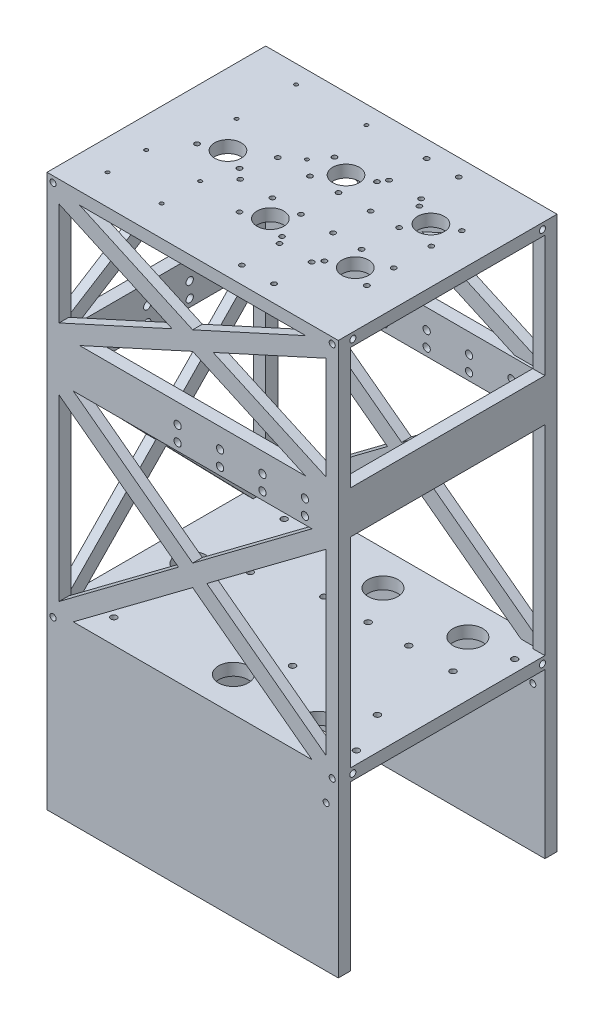
SolidWorks part; units mm, degrees
ref_plane "Front Plane" through (0, 0, 0) normal (0, 0, 1) x (1, 0, 0)
ref_plane "Top Plane" through (0, 0, 0) normal (0, 1, 0) x (1, 0, 0)
ref_plane "Right Plane" through (0, 0, 0) normal (1, 0, 0) x (0, 0, -1)
sketch "Sketch1" plane through (0, 0, 0) normal (0, 1, 0) x (1, 0, 0)
  line L0 (0, 90.15) -> (0, -90.15) construction
  line L1 (-120.075, 0) -> (120.075, 0) construction
  line L2 (-120.075, 90.15) -> (120.075, 90.15)
  line L3 (120.075, 90.15) -> (120.075, -90.15)
  line L4 (120.075, -90.15) -> (-120.075, -90.15)
  line L5 (-120.075, -90.15) -> (-120.075, 90.15)
  dimension "D1" = 240.15
  dimension "D2" = 180.3
extrude "Boss-Extrude1" add sketch "Sketch1" along normal blind 145
sketch "Sketch2" plane through (0, 145, 0) normal (0, 1, 0) x (1, 0, 0)
  line L0 (0, 90.15) -> (0, -90.15) construction
  line L1 (120.075, 90.15) -> (-120.075, 90.15) construction
  line L2 (-120.075, -90.15) -> (120.075, -90.15) construction
  line L3 (-120.075, 0) -> (120.075, 0) construction
  line L4 (-120.075, 90.15) -> (-120.075, -90.15) construction
  line L5 (120.075, -90.15) -> (120.075, 90.15) construction
  line L6 (75.105, -61.65) -> (75.105, -90.15) construction
  line L7 (75.105, -61.65) -> (120.075, -61.65) construction
  line L8 (75.105, -61.65) -> (5.105, -61.65) construction
  circle A0 centre (75.105, -61.65) radius 12.25
  circle A1 centre (5.105, -61.65) radius 12.25
  circle A2 centre (75.105, 61.65) radius 12.25
  circle A3 centre (5.105, 61.65) radius 12.25
  circle A4 centre (-91.515, 0) radius 12.25
  dimension "D3" = 24.5
  dimension "24.5" = 24.5
  dimension "D6" = 24.5
  dimension "D7" = 28.56
  dimension "D1" = 44.97
  dimension "D2" = 28.5
  dimension "D4" = 70
extrude "Cut-Extrude1" cut sketch "Sketch2" against normal blind 120
sketch "Sketch3" plane through (120.075, 0, 0) normal (1, 0, 0) x (0, 0, -1)
  line L0 (0, 145) -> (0, 0) construction
  line L1 (-90.15, 145) -> (90.15, 145) construction
  line L2 (-90.15, 72.5) -> (90.15, 72.5) construction
  line L3 (-90.15, 145) -> (-90.15, 0) construction
  line L4 (90.15, 145) -> (90.15, 0) construction
  line L5 (-80.21, 135.06) -> (80.21, 135.06)
  line L6 (80.21, 135.06) -> (80.21, 0)
  line L7 (-90.15, 0) -> (90.15, 0) construction
  line L8 (80.21, 0) -> (-80.21, 0)
  line L9 (-80.21, 0) -> (-80.21, 135.06)
  dimension "D1" = 9.94
  dimension "D2" = 9.94
  dimension "D3" = 9.94
extrude "Cut-Extrude3" cut sketch "Sketch3" against normal blind 220
sketch "Sketch9" plane through (0, 145, 0) normal (0, 1, 0) x (1, 0, 0)
  line L0 (-120.075, 90.15) -> (120.075, 90.15)
  line L1 (120.075, 90.15) -> (120.075, -90.15)
  line L2 (120.075, -90.15) -> (-120.075, -90.15)
  line L3 (-120.075, -90.15) -> (-120.075, 90.15)
extrude "Boss-Extrude3" add sketch "Sketch9" along normal blind 310.134
sketch "Sketch14" plane through (0, 455.134, 0) normal (0, 1, 0) x (1, 0, 0)
  line L0 (75.105, 61.65) -> (75.105, 31.17) construction
  line L1 (-91.515, 0) -> (-61.035, 0) construction
  line L2 (75.105, -61.65) -> (75.105, -31.17) construction
  line L3 (5.105, -61.65) -> (5.105, -31.17) construction
  line L4 (5.105, 61.65) -> (5.105, 31.17) construction
  line L5 (-61.035, 0) -> (193.3968, 0) construction
  line L6 (75.105, 31.17) -> (75.105, -31.17) construction
  line L7 (5.105, 31.17) -> (5.105, -31.17) construction
  line L8 (-61.035, 0) -> (-61.035, -46.2698) construction
  line L9 (-120.075, 90.15) -> (-120.075, -90.15) construction
  line L10 (120.075, 90.15) -> (-120.075, 90.15) construction
  line L11 (-35.4221, 15.5) -> (14.5779, 15.5) construction
  line L12 (120.075, -90.15) -> (120.075, 90.15) construction
  line L13 (-120.075, -90.15) -> (120.075, -90.15) construction
  line L14 (-51.075, 75.1045) -> (-51.075, 26.1045) construction
  line L21 (-100.8557, 50.65) -> (-1.2943, 50.65) construction
  circle A0 centre (5.105, -31.17) radius 11
  circle A1 centre (75.105, 31.17) radius 11
  circle A3 centre (-61.035, 0) radius 11
  circle A5 centre (75.105, -31.17) radius 11
  circle A6 centre (92.605, -39.14) radius 2
  circle A7 centre (75.105, -61.65) radius 12.25 construction
  circle A8 centre (57.605, -39.14) radius 2
  circle A9 centre (-91.515, 0) radius 12.25 construction
  circle A10 centre (5.105, -61.65) radius 12.25 construction
  circle A11 centre (5.105, 31.17) radius 11
  circle A12 centre (5.105, 61.65) radius 12.25 construction
  circle A13 centre (92.605, 39.14) radius 2
  circle A14 centre (57.605, 39.14) radius 2
  circle A15 centre (22.605, -39.14) radius 2
  circle A16 centre (-12.395, -39.14) radius 2
  circle A17 centre (22.605, 39.14) radius 2
  circle A18 centre (-12.395, 39.14) radius 2
  circle A19 centre (-43.535, -7.97) radius 2
  circle A20 centre (-78.535, -7.97) radius 2
  circle A21 centre (-35.4221, 15.5) radius 2
  circle A22 centre (-8.9221, 15.5) radius 2
  circle A23 centre (-8.9221, -15.5) radius 2
  circle A24 centre (-35.4221, -15.5) radius 2
  circle A25 centre (14.5779, 15.5) radius 2
  circle A26 centre (41.0779, 15.5) radius 2
  circle A27 centre (41.0779, -15.5) radius 2
  circle A28 centre (14.5779, -15.5) radius 2
  circle A29 centre (64.5779, 15.5) radius 2
  circle A30 centre (91.0779, 15.5) radius 2
  circle A31 centre (91.0779, -15.5) radius 2
  circle A32 centre (64.5779, -15.5) radius 2
  circle A33 centre (53.075, -45.15) radius 2
  circle A34 centre (26.575, -45.15) radius 2
  circle A35 centre (26.575, -76.15) radius 2
  circle A36 centre (53.075, -76.15) radius 2
  circle A37 centre (53.075, 76.15) radius 2
  circle A38 centre (26.575, 76.15) radius 2
  circle A39 centre (26.575, 45.15) radius 2
  circle A40 centre (53.075, 45.15) radius 2
  circle A46 centre (-80.075, 75.15) radius 1.5
  circle A47 centre (-22.075, 75.15) radius 1.5
  circle A48 centre (-22.075, 26.15) radius 1.5
  circle A49 centre (-80.075, 26.15) radius 1.5
  point P101 (-51.075, 50.65)
  point P114 (-51.075, 50.65)
  dimension "D2" = 22
  dimension "D3" = 22
  dimension "D5" = 22
  dimension "D6" = 22
  dimension "D7" = 22
  dimension "D8" = 30.48
  dimension "D9" = 30.48
  dimension "D10" = 30.48
  dimension "D4" = 30.48
  dimension "D12" = 17.5
  dimension "D13" = 4
  dimension "D14" = 17.5
  dimension "D15" = 17.5
  dimension "D16" = 7.97
  dimension "D17" = 58
  dimension "D18" = 4
  dimension "D19" = 26.5
  dimension "D20" = 15.5
  dimension "D21" = 84.6529
  dimension "D22" = 74.65
  dimension "D25" = 4
  dimension "D26" = 4
  dimension "D27" = 26.5
  dimension "D28" = 67
  dimension "D29" = 31
  dimension "D30" = 4
  dimension "D31" = 31
  dimension "D32" = 4
  dimension "D33" = 14
  dimension "D34" = 14
  dimension "D35" = 67
  dimension "D36" = 146.65
  dimension "D37" = 49
  dimension "D38" = 3
  dimension "D39" = 40
  dimension "D40" = 15
  dimension "D1" = 30.48
  dimension "D11" = 7.97
  dimension "D24" = 50
  dimension "D23" = 3
extrude "Cut-Extrude6" cut sketch "Sketch14" against normal blind 11
sketch "Sketch15" plane through (0, 0, -90.15) normal (0, 0, -1) x (-1, 0, 0)
  line L0 (-120.075, 455.134) -> (120.075, 455.134) construction
  line L1 (-110.075, 445.134) -> (110.075, 445.134)
  line L2 (-110.075, 445.134) -> (-110.075, 344.894)
  line L3 (-110.075, 344.894) -> (110.075, 344.894)
  line L4 (110.075, 445.134) -> (110.075, 344.894)
  line L5 (-120.075, 455.134) -> (-120.075, 0) construction
  line L6 (120.075, 455.134) -> (120.075, 0) construction
  line L28 (-110.075, 145) -> (110.075, 145)
  line L29 (-110.075, 145) -> (-110.075, 309.844)
  line L30 (-110.075, 309.844) -> (110.075, 309.844)
  line L31 (110.075, 145) -> (110.075, 309.844)
  dimension "D1" = 110.24
  dimension "D2" = 10
  dimension "D3" = 10
  dimension "D4" = 10
  dimension "D5" = 10
  dimension "D6" = 35.05
  dimension "D7" = 10
  dimension "D8" = 164.844
extrude "Cut-Extrude7" cut sketch "Sketch15" against normal through all
sketch "Sketch16" plane through (120.075, 0, 0) normal (1, 0, 0) x (0, 0, -1)
  line L0 (-90.15, 455.134) -> (-90.15, 0) construction
  line L1 (-80.15, 445.134) -> (80.15, 445.134)
  line L2 (-80.15, 445.134) -> (-80.15, 344.894)
  line L3 (-80.15, 344.894) -> (80.15, 344.894)
  line L4 (80.15, 445.134) -> (80.15, 344.894)
  line L5 (-8.907, 135.06) -> (-80.21, 135.06) construction
  line L6 (90.15, 455.134) -> (90.15, 0) construction
  line L7 (-90.15, 455.134) -> (90.15, 455.134) construction
  line L27 (-80.15, 145) -> (80.15, 145)
  line L28 (-80.15, 145) -> (-80.15, 309.842)
  line L29 (-80.15, 309.842) -> (80.15, 309.842)
  line L30 (80.15, 145) -> (80.15, 309.842)
  dimension "D1" = 10
  dimension "D2" = 10
  dimension "D3" = 10
  dimension "D4" = 110.24
  dimension "D5" = 164.842
  dimension "D6" = 160.3
  dimension "D7" = 10
  dimension "D8" = 9.94
extrude "Cut-Extrude8" cut sketch "Sketch16" against normal through all
sketch "Sketch17" plane through (0, 344.894, 0) normal (0, 1, 0) x (1, 0, 0)
  line L0 (-120.075, 90.15) -> (-120.075, -90.15) construction
  line L1 (-110.075, 80.15) -> (110.075, 80.15)
  line L2 (-110.075, 80.15) -> (-110.075, -80.15)
  line L3 (-110.075, -80.15) -> (110.075, -80.15)
  line L4 (110.075, 80.15) -> (110.075, -80.15)
  line L5 (120.075, 90.15) -> (-120.075, 90.15) construction
  line L6 (120.075, -90.15) -> (120.075, 90.15) construction
  line L7 (-120.075, -90.15) -> (120.075, -90.15) construction
  dimension "D1" = 10
  dimension "D2" = 10
  dimension "D3" = 10
  dimension "D4" = 10
extrude "Cut-Extrude9" cut sketch "Sketch17" against normal up to next
sketch "Sketch18" plane through (0, 0, 90.15) normal (0, 0, 1) x (1, 0, 0)
  line L0 (-110.075, 309.844) -> (110.075, 309.844) construction
  line L1 (-12.395, 316.144) -> (22.605, 316.144) construction
  line L2 (120.075, 455.134) -> (120.075, 0) construction
  line L3 (22.605, 316.144) -> (57.605, 316.144) construction
  line L4 (57.605, 316.144) -> (92.605, 316.144) construction
  line L5 (-120.075, 322.394) -> (120.075, 322.394) construction
  line L6 (-120.075, 455.134) -> (-120.075, 0) construction
  circle A0 centre (-12.395, 316.144) radius 3
  circle A1 centre (22.605, 316.144) radius 3
  circle A2 centre (57.605, 316.144) radius 3
  circle A3 centre (92.605, 316.144) radius 3
  circle A4 centre (92.605, 328.644) radius 3
  circle A5 centre (57.605, 328.644) radius 3
  circle A6 centre (22.605, 328.644) radius 3
  circle A7 centre (-12.395, 328.644) radius 3
  dimension "D3" = 6.3
  dimension "D4" = 6.3
  dimension "D5" = 35
  dimension "D6" = 35
  dimension "D1" = 27.47
  dimension "D7" = 6.3
  dimension "D8" = 6.3
  dimension "D9" = 35
  dimension "D2" = 6
  dimension "D10" = 6.25
extrude "Cut-Extrude10" cut sketch "Sketch18" against normal blind 249
sketch "Sketch19" plane through (-120.075, 0, 0) normal (-1, 0, 0) x (0, 0, 1)
  line L0 (-90.15, 322.392) -> (90.15, 322.392) construction
  line L1 (-90.15, 455.134) -> (-90.15, 0) construction
  line L2 (-80.15, 309.842) -> (80.15, 309.842) construction
  line L3 (90.15, 455.134) -> (90.15, 0) construction
  circle A0 centre (-17.5, 316.142) radius 3
  circle A1 centre (17.5, 316.142) radius 3
  circle A2 centre (17.5, 328.642) radius 3
  circle A3 centre (-17.5, 328.642) radius 3
  dimension "D1" = 6
  dimension "D2" = 72.65
  dimension "D3" = 35
  dimension "D4" = 6
  dimension "D5" = 6.3
  dimension "D6" = 6.3
  dimension "D7" = 6.25
extrude "Cut-Extrude11" cut sketch "Sketch19" against normal blind 104
sketch "Sketch21" plane through (0, 0, 90.15) normal (0, 0, 1) x (1, 0, 0)
  line L0 (-120.075, 455.134) -> (120.075, 455.134) construction
  line L1 (-120.075, 455.134) -> (-120.075, 0) construction
  line L2 (120.075, 455.134) -> (120.075, 0) construction
  line L3 (110.075, 145) -> (-110.075, 145) construction
  circle A0 centre (-115.075, 450.134) radius 2.5
  circle A1 centre (115.075, 450.134) radius 2.5
  circle A2 centre (-115.075, 140) radius 2.5
  circle A3 centre (115.075, 140) radius 2.5
  dimension "D1" = 5
  dimension "D2" = 5
  dimension "D3" = 5
  dimension "D4" = 5
  dimension "D5" = 5
  dimension "D6" = 5
  dimension "D7" = 5
  dimension "D8" = 5
  dimension "D9" = 5
  dimension "D10" = 5
  dimension "D11" = 5
  dimension "D12" = 5
extrude "Cut-Extrude12" cut sketch "Sketch21" against normal blind 8
sketch "Sketch22" plane through (-120.075, 0, 0) normal (-1, 0, 0) x (0, 0, 1)
  line L0 (-90.15, 455.134) -> (90.15, 455.134) construction
  line L1 (-90.15, 455.134) -> (-90.15, 0) construction
  line L2 (90.15, 455.134) -> (90.15, 0) construction
  line L4 (80.15, 145) -> (-80.15, 145) construction
  circle A0 centre (-78.15, 450.134) radius 2.5
  circle A1 centre (78.15, 450.134) radius 2.5
  circle A2 centre (-78.15, 140) radius 2.5
  circle A3 centre (78.15, 140) radius 2.5
  dimension "D1" = 5
  dimension "D2" = 5
  dimension "D3" = 12
  dimension "D4" = 5
  dimension "D6" = 5
  dimension "D7" = 5
  dimension "D8" = 12
  dimension "D9" = 5
  dimension "D10" = 5
  dimension "D11" = 5
  dimension "D12" = 12
  dimension "D5" = 12
extrude "Cut-Extrude13" cut sketch "Sketch22" against normal blind 8
sketch "Sketch23" plane through (0, 0, -90.15) normal (0, 0, -1) x (-1, 0, 0)
  line L0 (-120.075, 455.134) -> (120.075, 455.134) construction
  line L1 (-120.075, 455.134) -> (-120.075, 0) construction
  line L2 (120.075, 455.134) -> (120.075, 0) construction
  line L4 (-110.075, 145) -> (110.075, 145) construction
  circle A0 centre (-115.075, 450.134) radius 2.5
  circle A1 centre (115.075, 450.134) radius 2.5
  circle A2 centre (-115.075, 140) radius 2.5
  circle A3 centre (115.075, 140) radius 2.5
  dimension "D1" = 5
  dimension "D2" = 5
  dimension "D3" = 5
  dimension "D4" = 5
  dimension "D5" = 5
  dimension "D6" = 5
  dimension "D7" = 5
  dimension "D8" = 5
  dimension "D9" = 5
  dimension "D10" = 5
  dimension "D11" = 5
  dimension "D12" = 5
extrude "Cut-Extrude14" cut sketch "Sketch23" against normal blind 8
sketch "Sketch24" plane through (120.075, 0, 0) normal (1, 0, 0) x (0, 0, -1)
  line L0 (-90.15, 455.134) -> (90.15, 455.134) construction
  line L1 (-90.15, 455.134) -> (-90.15, 0) construction
  line L2 (90.15, 455.134) -> (90.15, 0) construction
  line L4 (-80.15, 145) -> (80.15, 145) construction
  circle A0 centre (-78.15, 450.134) radius 2.5
  circle A1 centre (78.15, 450.134) radius 2.5
  circle A2 centre (-78.15, 140) radius 2.5
  circle A3 centre (78.15, 140) radius 2.5
  dimension "D1" = 5
  dimension "D2" = 5
  dimension "D3" = 12
  dimension "D4" = 5
  dimension "D5" = 5
  dimension "D6" = 12
  dimension "D7" = 5
  dimension "D8" = 12
  dimension "D9" = 5
  dimension "D10" = 5
  dimension "D11" = 5
  dimension "D12" = 12
extrude "Cut-Extrude15" cut sketch "Sketch24" against normal blind 8
sketch "Sketch25" plane through (0, 0, 90.15) normal (0, 0, 1) x (1, 0, 0)
  line L0 (-110.075, 309.844) -> (110.075, 145) construction
  line L1 (110.075, 309.844) -> (-110.075, 145) construction
  line L2 (-110.075, 301.0991) -> (-11.6788, 227.422)
  line L3 (-110.075, 145) -> (-110.075, 309.844) construction
  line L4 (110.075, 145) -> (-110.075, 145) construction
  line L5 (-98.3962, 309.844) -> (0, 236.1669)
  line L6 (-110.075, 309.844) -> (110.075, 309.844) construction
  line L7 (110.075, 309.844) -> (110.075, 145) construction
  line L8 (-110.075, 153.7449) -> (-11.6788, 227.422)
  line L9 (-98.3962, 145) -> (0, 218.6771)
  line L10 (11.6788, 227.422) -> (110.075, 153.7449)
  line L11 (11.6788, 227.422) -> (110.075, 301.0991)
  line L12 (0, 218.6771) -> (98.3962, 145)
  line L13 (0, 236.1669) -> (98.3962, 309.844)
  line L14 (-110.075, 153.7449) -> (-110.075, 145)
  line L15 (-110.075, 145) -> (-98.3962, 145)
  line L16 (-110.075, 301.0991) -> (-110.075, 309.844)
  line L17 (-110.075, 309.844) -> (-98.3962, 309.844)
  line L18 (98.3962, 309.844) -> (110.075, 309.844)
  line L19 (110.075, 309.844) -> (110.075, 301.0991)
  line L20 (98.3962, 145) -> (110.075, 145)
  line L21 (110.075, 145) -> (110.075, 153.7449)
  dimension "D1" = 7
  dimension "D2" = 7
  dimension "D3" = 7
  dimension "D4" = 7
extrude "Boss-Extrude4" add sketch "Sketch25" against normal blind 8
sketch "Sketch26" plane through (0, 0, -90.15) normal (0, 0, -1) x (-1, 0, 0)
  line L0 (-110.075, 309.844) -> (110.075, 145) construction
  line L1 (110.075, 309.844) -> (-110.075, 145) construction
  line L2 (-110.075, 301.0991) -> (-11.6788, 227.422)
  line L3 (-98.3962, 309.844) -> (0, 236.1669)
  line L4 (-110.075, 153.7449) -> (-11.6788, 227.422)
  line L5 (-98.3962, 145) -> (0, 218.6771)
  line L6 (11.6788, 227.422) -> (110.075, 153.7449)
  line L7 (11.6788, 227.422) -> (110.075, 301.0991)
  line L8 (0, 218.6771) -> (98.3962, 145)
  line L9 (0, 236.1669) -> (98.3962, 309.844)
  line L10 (-110.075, 153.7449) -> (-110.075, 145)
  line L11 (-110.075, 145) -> (-98.3962, 145)
  line L12 (-110.075, 301.0991) -> (-110.075, 309.844)
  line L13 (-110.075, 309.844) -> (-98.3962, 309.844)
  line L14 (98.3962, 309.844) -> (110.075, 309.844)
  line L15 (110.075, 309.844) -> (110.075, 301.0991)
  line L16 (98.3962, 145) -> (110.075, 145)
  line L17 (110.075, 145) -> (110.075, 153.7449)
  line L18 (-110.075, 309.844) -> (-110.075, 145) construction
  line L19 (-110.075, 344.894) -> (110.075, 344.894) construction
  line L20 (-120.075, 0) -> (120.075, 0) construction
  dimension "D1" = 7
  dimension "D2" = 7
  dimension "D3" = 7
  dimension "D4" = 7
  dimension "D5" = 53.175
  dimension "D6" = 53.175
  dimension "D7" = 35.05
  dimension "D8" = 145
extrude "Boss-Extrude5" add sketch "Sketch26" against normal blind 8
sketch "Sketch27" plane through (-120.075, 0, 0) normal (-1, 0, 0) x (0, 0, 1)
  line L0 (-80.15, 309.842) -> (80.15, 145) construction
  line L1 (80.15, 309.842) -> (-80.15, 145) construction
  line L2 (-80.15, 301.2532) -> (-8.3522, 227.421)
  line L3 (-80.15, 145) -> (-80.15, 309.842) construction
  line L4 (80.15, 145) -> (-80.15, 145) construction
  line L5 (-71.7978, 309.842) -> (0, 236.0098)
  line L6 (-80.15, 309.842) -> (80.15, 309.842) construction
  line L7 (80.15, 309.842) -> (80.15, 145) construction
  line L8 (71.7978, 309.842) -> (0, 236.0098)
  line L9 (80.15, 301.2532) -> (8.3522, 227.421)
  line L10 (-80.15, 301.2532) -> (-80.15, 309.842)
  line L11 (-80.15, 309.842) -> (-71.7978, 309.842)
  line L12 (71.7978, 309.842) -> (80.15, 309.842)
  line L13 (80.15, 309.842) -> (80.15, 301.2532)
  line L14 (80.15, 153.5888) -> (80.15, 145)
  line L15 (80.15, 145) -> (71.7978, 145)
  line L16 (-80.15, 153.5888) -> (-80.15, 145)
  line L17 (-80.15, 145) -> (-71.7978, 145)
  line L18 (8.3522, 227.421) -> (80.15, 153.5888)
  line L19 (0, 218.8322) -> (71.7978, 145)
  line L20 (-8.3522, 227.421) -> (-80.15, 153.5888)
  line L21 (0, 218.8322) -> (-71.7978, 145)
  dimension "D1" = 5.9878
  dimension "D2" = 5.9878
  dimension "D3" = 5.9878
  dimension "D4" = 5.9878
extrude "Boss-Extrude6" add sketch "Sketch27" against normal blind 8
sketch "Sketch29" plane through (-120.075, 0, 0) normal (-1, 0, 0) x (0, 0, 1)
  line L0 (-80.15, 445.134) -> (80.15, 344.894) construction
  line L1 (80.15, 445.134) -> (-80.15, 344.894) construction
  line L2 (-80.15, 438.0719) -> (-11.2935, 395.014)
  line L3 (-68.8565, 445.134) -> (0, 402.0761)
  line L4 (68.8565, 445.134) -> (0, 402.0761)
  line L5 (80.15, 438.0719) -> (11.2935, 395.014)
  line L6 (-80.15, 438.0719) -> (-80.15, 445.134)
  line L7 (-80.15, 445.134) -> (-68.8565, 445.134)
  line L8 (68.8565, 445.134) -> (80.15, 445.134)
  line L9 (80.15, 445.134) -> (80.15, 438.0719)
  line L10 (80.15, 351.9561) -> (80.15, 344.894)
  line L11 (80.15, 344.894) -> (68.8565, 344.894)
  line L12 (-80.15, 351.9561) -> (-80.15, 344.894)
  line L13 (-80.15, 344.894) -> (-68.8565, 344.894)
  line L14 (11.2935, 395.014) -> (80.15, 351.9561)
  line L15 (0, 387.9519) -> (68.8565, 344.894)
  line L16 (-11.2935, 395.014) -> (-80.15, 351.9561)
  line L17 (0, 387.9519) -> (-68.8565, 344.894)
  dimension "D1" = 5.9878
  dimension "D2" = 5.9878
  dimension "D3" = 5.9878
  dimension "D4" = 5.9878
extrude "Boss-Extrude7" add sketch "Sketch29" against normal blind 8
sketch "Sketch30" plane through (0, 0, -90.15) normal (0, 0, -1) x (-1, 0, 0)
  line L0 (-110.075, 445.134) -> (110.075, 344.894) construction
  line L1 (110.075, 445.134) -> (-110.075, 344.894) construction
  line L2 (-110.075, 437.4425) -> (-16.8922, 395.014)
  line L3 (-93.1828, 445.134) -> (0, 402.7055)
  line L4 (-110.075, 352.5855) -> (-16.8922, 395.014)
  line L5 (-93.1828, 344.894) -> (0, 387.3225)
  line L6 (16.8922, 395.014) -> (110.075, 352.5855)
  line L7 (16.8922, 395.014) -> (110.075, 437.4425)
  line L8 (0, 387.3225) -> (93.1828, 344.894)
  line L9 (0, 402.7055) -> (93.1828, 445.134)
  line L10 (-110.075, 352.5855) -> (-110.075, 344.894)
  line L11 (-110.075, 344.894) -> (-93.1828, 344.894)
  line L12 (-110.075, 437.4425) -> (-110.075, 445.134)
  line L13 (-110.075, 445.134) -> (-93.1828, 445.134)
  line L14 (93.1828, 445.134) -> (110.075, 445.134)
  line L15 (110.075, 445.134) -> (110.075, 437.4425)
  line L16 (93.1828, 344.894) -> (110.075, 344.894)
  line L17 (110.075, 344.894) -> (110.075, 352.5855)
  dimension "D1" = 7
  dimension "D2" = 7
  dimension "D3" = 7
  dimension "D4" = 7
extrude "Boss-Extrude8" add sketch "Sketch30" against normal blind 8
sketch "Sketch31" plane through (0, 0, 90.15) normal (0, 0, 1) x (1, 0, 0)
  line L0 (-110.075, 445.134) -> (110.075, 344.894) construction
  line L1 (110.075, 445.134) -> (-110.075, 344.894) construction
  line L2 (-110.075, 437.4425) -> (-16.8922, 395.014)
  line L3 (-93.1828, 445.134) -> (0, 402.7055)
  line L4 (-110.075, 352.5855) -> (-16.8922, 395.014)
  line L5 (-93.1828, 344.894) -> (0, 387.3225)
  line L6 (16.8922, 395.014) -> (110.075, 352.5855)
  line L7 (16.8922, 395.014) -> (110.075, 437.4425)
  line L8 (0, 387.3225) -> (93.1828, 344.894)
  line L9 (0, 402.7055) -> (93.1828, 445.134)
  line L10 (-110.075, 352.5855) -> (-110.075, 344.894)
  line L11 (-110.075, 344.894) -> (-93.1828, 344.894)
  line L12 (-110.075, 437.4425) -> (-110.075, 445.134)
  line L13 (-110.075, 445.134) -> (-93.1828, 445.134)
  line L14 (93.1828, 445.134) -> (110.075, 445.134)
  line L15 (110.075, 445.134) -> (110.075, 437.4425)
  line L16 (93.1828, 344.894) -> (110.075, 344.894)
  line L17 (110.075, 344.894) -> (110.075, 352.5855)
  dimension "D1" = 7
  dimension "D2" = 7
  dimension "D3" = 7
  dimension "D4" = 7
extrude "Boss-Extrude9" add sketch "Sketch31" against normal blind 8
sketch "Sketch32" plane through (0, 145, 0) normal (0, 1, 0) x (1, 0, 0)
  line L0 (120.075, -90.15) -> (120.075, 90.15) construction
  line L1 (120.075, 90.15) -> (-120.075, 90.15) construction
  line L2 (120.075, 0) -> (-120.075, 0) construction
  line L3 (-120.075, 90.15) -> (-120.075, -90.15) construction
  circle A0 centre (93.355, 31.14) radius 2.5
  circle A1 centre (56.855, 31.14) radius 2.5
  circle A2 centre (23.355, 31.14) radius 2.5
  circle A3 centre (-13.145, 31.14) radius 2.5
  circle A4 centre (-13.145, -31.14) radius 2.5
  circle A5 centre (23.355, -31.14) radius 2.5
  circle A6 centre (56.855, -31.14) radius 2.5
  circle A7 centre (93.355, -31.14) radius 2.5
  circle A15 centre (-61.005, -18.25) radius 2.5
  circle A16 centre (-61.035, 0) radius 11 construction
  circle A18 centre (-61.005, 18.25) radius 2.5
  dimension "D2" = 59.01
  dimension "D3" = 5
  dimension "D4" = 5
  dimension "D5" = 36.5
  dimension "D6" = 59.01
  dimension "D7" = 5
  dimension "D8" = 33.5
  dimension "D9" = 59.01
  dimension "D10" = 5
  dimension "D11" = 36.5
  dimension "D12" = 59.01
  dimension "D13" = 5
  dimension "D14" = 59.07
  dimension "D15" = 18.25
  dimension "D1" = 26.72
extrude "Cut-Extrude16" cut sketch "Sketch32" against normal up to next
sketch "Sketch33" plane through (0, 0, 80.21) normal (0, 0, -1) x (-1, 0, 0)
  line L0 (99.925, 135.06) -> (-120.075, 135.06) construction
  line L1 (-120.075, 135.06) -> (-120.075, 0) construction
  circle A0 centre (-110.075, 120.06) radius 2.5
  dimension "D1" = 5
  dimension "D2" = 15
  dimension "D3" = 10
extrude "Cut-Extrude17" cut sketch "Sketch33" against normal through all both and the other way through all
sketch "Sketch34" plane through (-99.925, 0, 0) normal (1, 0, 0) x (0, 0, -1)
  line L0 (-8.907, 135.06) -> (-80.21, 135.06) construction
  line L1 (-80.21, 135.06) -> (-80.21, 0) construction
  line L2 (80.21, 135.06) -> (8.907, 135.06) construction
  line L3 (80.21, 0) -> (80.21, 135.06) construction
  circle A0 centre (-70.21, 120.06) radius 2.5
  circle A1 centre (70.21, 120.06) radius 2.5
  dimension "D1" = 5
  dimension "D2" = 15
  dimension "D4" = 5
  dimension "D5" = 15
  dimension "D6" = 10
  dimension "D3" = 10
extrude "Cut-Extrude18" cut sketch "Sketch34" against normal through all and the other way through all
sketch "Sketch35" plane through (0, 135.06, 0) normal (0, -1, 0) x (1, 0, 0)
  line L0 (-99.925, 80.21) -> (120.075, 80.21) construction
  line L1 (-99.925, 80.21) -> (120.075, 80.21) construction
  line L2 (-99.925, -80.21) -> (120.075, -80.21) construction
  line L3 (-99.925, -80.21) -> (120.075, -80.21) construction
  line L4 (120.075, -80.21) -> (120.075, 80.21) construction
  line L5 (-99.925, -80.21) -> (-99.925, -8.907) construction
  line L6 (-99.925, 8.907) -> (-99.925, 80.21) construction
  circle A0 centre (110.075, 65.21) radius 2.5
  circle A1 centre (110.075, -65.21) radius 2.5
  circle A2 centre (-84.925, -70.21) radius 2.5
  circle A3 centre (-84.925, 70.21) radius 2.5
  dimension "D1" = 5
  dimension "D2" = 5
  dimension "D3" = 5
  dimension "D4" = 5
  dimension "D5" = 15
  dimension "D6" = 10
  dimension "D7" = 10
  dimension "D8" = 15
  dimension "D9" = 10
  dimension "D10" = 10
  dimension "D11" = 15
  dimension "D12" = 15
extrude "Cut-Extrude19" cut sketch "Sketch35" against normal blind 10
sketch "Sketch37" plane through (0, 455.134, 0) normal (0, 1, 0) x (1, 0, 0)
  line L0 (-50.575, -65.15) -> (-50.575, -33.35) construction
  line L1 (-50.575, -33.35) -> (-95.075, -33.35) construction
  line L2 (-95.075, -33.35) -> (-95.075, -65.15) construction
  line L3 (-95.075, -65.15) -> (-50.575, -65.15) construction
  line L4 (-120.075, -90.15) -> (120.075, -90.15) construction
  line L5 (-120.075, 90.15) -> (-120.075, -90.15) construction
  circle A0 centre (-95.075, -33.35) radius 1.5
  circle A1 centre (-50.575, -33.35) radius 1.5
  circle A2 centre (-95.075, -65.15) radius 1.5
  circle A3 centre (-50.575, -65.15) radius 1.5
  point P8 (0, 0)
  point P11 (0, 0)
  point P12 (0, 0)
  dimension "D1" = 3
  dimension "D2" = 44.5
  dimension "D3" = 31.8
  dimension "D4" = 25
  dimension "D5" = 25
extrude "Cut-Extrude20" cut sketch "Sketch37" against normal blind 10
